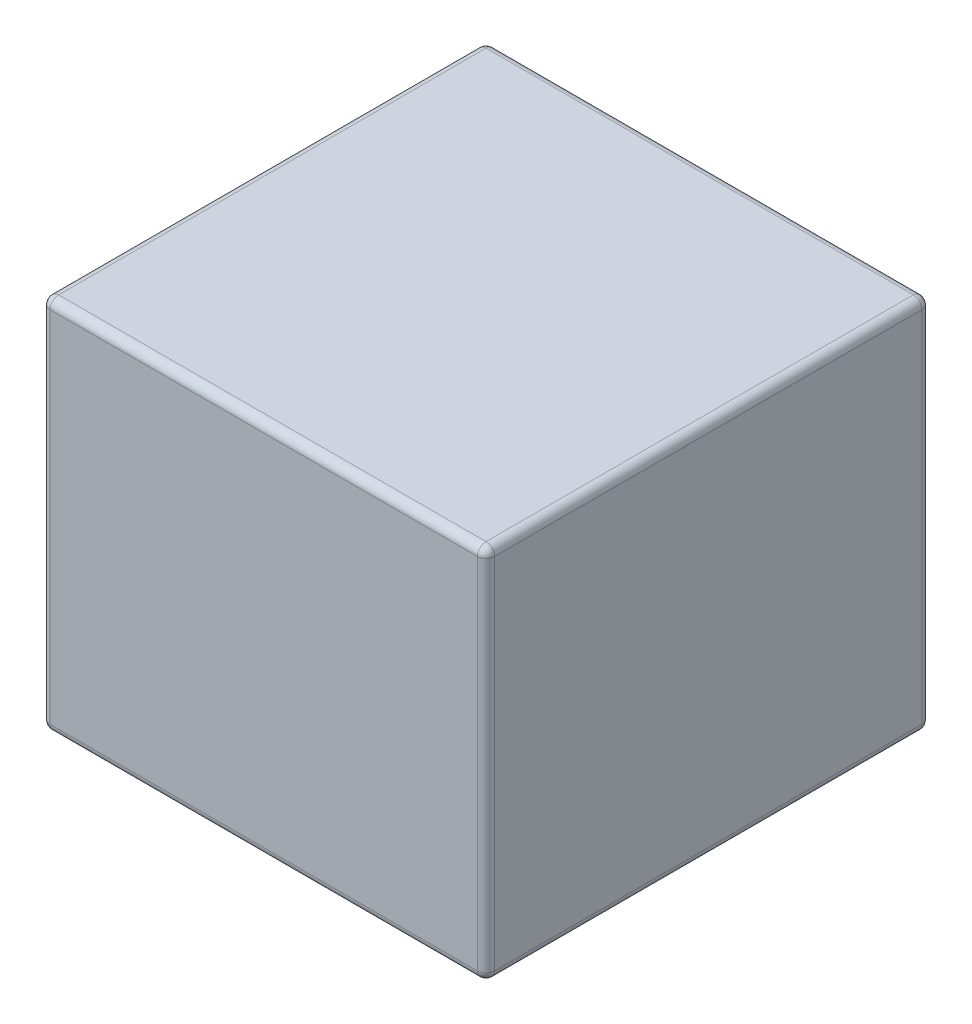
SolidWorks part; units mm, degrees
ref_plane "Front Plane" through (0, 0, 0) normal (0, 0, 1) x (1, 0, 0)
ref_plane "Top Plane" through (0, 0, 0) normal (0, 1, 0) x (1, 0, 0)
ref_plane "Right Plane" through (0, 0, 0) normal (1, 0, 0) x (0, 0, -1)
sketch "Sketch1" plane through (0, 0, 0) normal (0, 1, 0) x (1, 0, 0)
  line L1 (0, 0) -> (330.2, 0)
  line L2 (0, 0) -> (0, 330.2)
  line L3 (0, 330.2) -> (330.2, 330.2)
  line L4 (330.2, 0) -> (330.2, 330.2)
  dimension "D1" = 330.2
  dimension "D2" = 330.2
extrude "Boss-Extrude1" add sketch "Sketch1" along normal blind 279.4
fillet "Fillet1" radius 6.35 12 edges at (0, 0, -165.1) (0, 139.7, -330.2) (165.1, 0, -330.2) (330.2, 139.7, -330.2) (330.2, 0, -165.1) (0, 139.7, 0) (330.2, 139.7, 0) (165.1, 0, 0) (165.1, 279.4, -330.2) (330.2, 279.4, -165.1) (165.1, 279.4, 0) (0, 279.4, -165.1)
ref_plane "Mid_Plane" through (165.1, 0, 0) normal (1, 0, 0) x (0, 0, -1)
